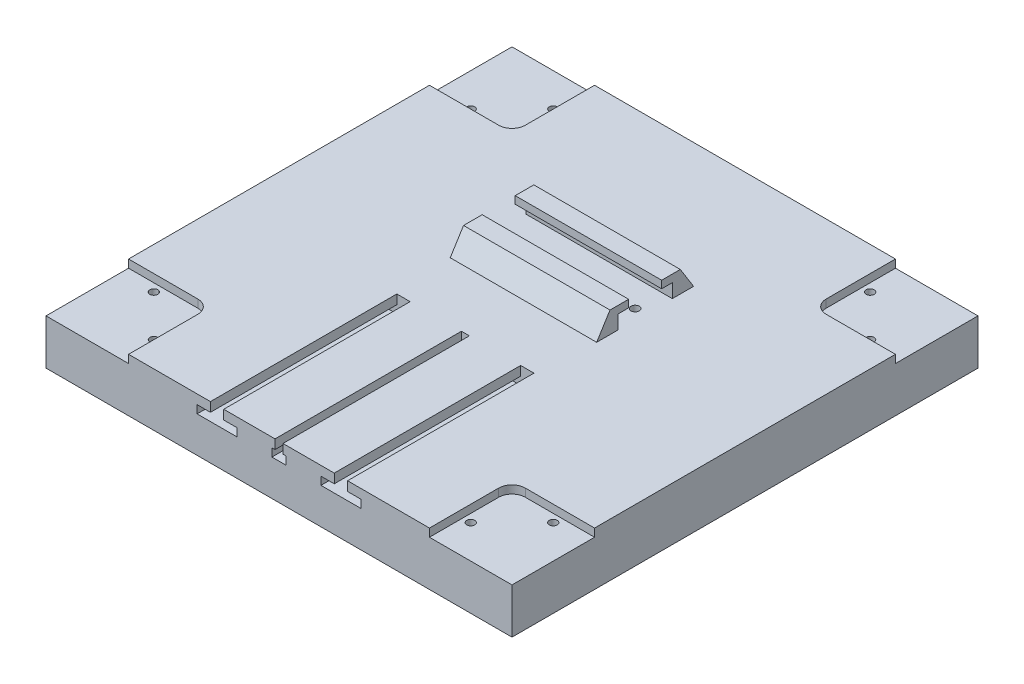
SolidWorks part; units mm, degrees
ref_plane "Front Plane" through (0, 0, 0) normal (0, 0, 1) x (1, 0, 0)
ref_plane "Top Plane" through (0, 0, 0) normal (0, 1, 0) x (1, 0, 0)
ref_plane "Right Plane" through (0, 0, 0) normal (1, 0, 0) x (0, 0, -1)
sketch "Sketch1" plane through (0, 0, 0) normal (0, 1, 0) x (1, 0, 0)
  line L0 (0, 87.5) -> (0, -87.5) construction
  line L1 (-87.5, 87.5) -> (87.5, 87.5)
  line L2 (-87.5, 87.5) -> (-87.5, -87.5)
  line L3 (-87.5, -87.5) -> (87.5, -87.5)
  line L4 (87.5, 87.5) -> (87.5, -87.5)
  line L5 (-87.5, 87.5) -> (87.5, -87.5) construction
  line L6 (-87.5, -87.5) -> (87.5, 87.5) construction
  line L15 (-87.5, 0) -> (87.5, 0) construction
  point P0 (0, 0)
  dimension "D1" = 175
  dimension "D2" = 175
extrude "Boss-Extrude2" add sketch "Sketch1" along normal blind 20
sketch "Sketch7" plane through (0, 20, 0) normal (0, 1, 0) x (1, 0, 0)
  line L0 (0, 87.5) -> (0, -87.5) construction
  line L1 (-87.5, 87.5) -> (-56.5, 87.5)
  line L2 (-87.5, 87.5) -> (-87.5, 56.5)
  line L3 (-87.5, 56.5) -> (-61.5, 56.5)
  line L4 (-56.5, 87.5) -> (-56.5, 61.5)
  line L5 (87.5, 87.5) -> (-87.5, 87.5) construction
  line L6 (-87.5, -87.5) -> (87.5, -87.5) construction
  line L7 (-87.5, 0) -> (87.5, 0) construction
  line L8 (-87.5, 87.5) -> (-87.5, -87.5) construction
  line L9 (87.5, -87.5) -> (87.5, 87.5) construction
  line L10 (87.5, 56.5) -> (61.5, 56.5)
  line L11 (56.5, 87.5) -> (56.5, 61.5)
  line L12 (87.5, 87.5) -> (56.5, 87.5)
  line L13 (87.5, 87.5) -> (87.5, 56.5)
  line L14 (87.5, -87.5) -> (87.5, -56.5)
  line L15 (87.5, -87.5) -> (56.5, -87.5)
  line L16 (56.5, -87.5) -> (56.5, -61.5)
  line L17 (87.5, -56.5) -> (61.5, -56.5)
  line L18 (-56.5, -87.5) -> (-56.5, -61.5)
  line L19 (-87.5, -56.5) -> (-61.5, -56.5)
  line L20 (-87.5, -87.5) -> (-87.5, -56.5)
  line L21 (-87.5, -87.5) -> (-56.5, -87.5)
  arc A0 (-61.5, 56.5) -> (-56.5, 61.5) centre (-61.5, 61.5) ccw
  arc A1 (61.5, 56.5) -> (56.5, 61.5) centre (61.5, 61.5) cw
  arc A2 (61.5, -56.5) -> (56.5, -61.5) centre (61.5, -61.5) ccw
  arc A3 (-61.5, -56.5) -> (-56.5, -61.5) centre (-61.5, -61.5) cw
  point P7 (-56.5, 56.5)
  point P38 (-56.5, -56.5)
  dimension "D3" = 5
  dimension "D1" = 31
  dimension "D2" = 31
extrude "Cut-Extrude6" cut sketch "Sketch7" against normal blind 3
sketch "Sketch8" plane through (0, 17, 0) normal (0, 1, 0) x (1, 0, 0)
  line L0 (-75, -62.5) -> (-75, -56.5) construction
  line L5 (-61.5, -56.5) -> (-87.5, -56.5) construction
  line L6 (-62.5, -75) -> (-56.5, -75) construction
  line L7 (-56.5, -87.5) -> (-56.5, -61.5) construction
  line L8 (-87.5, -87.5) -> (-56.5, -87.5) construction
  line L9 (-87.5, -56.5) -> (-87.5, -87.5) construction
  line L10 (0, 87.5) -> (0, -87.5) construction
  line L11 (56.5, 87.5) -> (-56.5, 87.5) construction
  line L12 (-56.5, -87.5) -> (56.5, -87.5) construction
  line L13 (62.5, -75) -> (56.5, -75) construction
  line L14 (75, -62.5) -> (75, -56.5) construction
  line L15 (-87.5, 0) -> (87.5, 0) construction
  line L16 (-87.5, 56.5) -> (-87.5, -56.5) construction
  line L17 (87.5, -56.5) -> (87.5, 56.5) construction
  circle A0 centre (-75, -59.5) radius 1.5
  circle A1 centre (-59.5, -75) radius 1.5
  circle A2 centre (59.5, -75) radius 1.5
  circle A3 centre (75, -59.5) radius 1.5
  circle A4 centre (59.5, 75) radius 1.5
  circle A5 centre (75, 59.5) radius 1.5
  circle A6 centre (-59.5, 75) radius 1.5
  circle A7 centre (-75, 59.5) radius 1.5
  dimension "D3" = 3
  dimension "D4" = 3
  dimension "D1" = 28
  dimension "D2" = 28
  dimension "D5" = 12.5
  dimension "D6" = 12.5
extrude "Cut-Extrude7" cut sketch "Sketch8" against normal up to next
sketch "Sketch9" plane through (0, 0, 87.5) normal (0, 0, 1) x (1, 0, 0)
  line L0 (0, 20) -> (0, 0) construction
  line L1 (-56.5, 20) -> (56.5, 20) construction
  line L2 (0, 10) -> (-46.5, 10) construction
  line L3 (-46.5, 20) -> (46.5, 20)
  line L4 (-46.5, 20) -> (-46.5, 0)
  line L5 (-46.5, 0) -> (46.5, 0)
  line L6 (46.5, 20) -> (46.5, 0)
  line L7 (-46.5, 20) -> (46.5, 0) construction
  line L8 (-46.5, 0) -> (46.5, 20) construction
  line L9 (-46.5, 10) -> (0, 10) construction
  line L10 (-20.75, 16.5) -> (-15.75, 16.5)
  line L11 (-23.25, 10) -> (-23.25, 20) construction
  line L12 (-30.75, 16.5) -> (-25.75, 16.5)
  line L13 (-30.75, 16.5) -> (-30.75, 13.5)
  line L14 (-30.75, 13.5) -> (-15.75, 13.5)
  line L15 (-15.75, 16.5) -> (-15.75, 13.5)
  line L16 (-30.75, 16.5) -> (-15.75, 13.5) construction
  line L17 (-30.75, 13.5) -> (-15.75, 16.5) construction
  line L18 (-25.75, 20) -> (-20.75, 20)
  line L19 (-25.75, 20) -> (-25.75, 16.5)
  line L21 (-20.75, 20) -> (-20.75, 16.5)
  line L22 (-25.75, 20) -> (-20.75, 16.5) construction
  line L23 (-25.75, 16.5) -> (-20.75, 20) construction
  line L24 (25.75, 16.5) -> (20.75, 20) construction
  line L25 (25.75, 20) -> (20.75, 16.5) construction
  line L26 (30.75, 13.5) -> (15.75, 16.5) construction
  line L27 (30.75, 16.5) -> (15.75, 13.5) construction
  line L28 (20.75, 20) -> (20.75, 16.5)
  line L29 (25.75, 20) -> (25.75, 16.5)
  line L30 (25.75, 20) -> (20.75, 20)
  line L31 (15.75, 16.5) -> (15.75, 13.5)
  line L32 (30.75, 13.5) -> (15.75, 13.5)
  line L33 (30.75, 16.5) -> (30.75, 13.5)
  line L34 (30.75, 16.5) -> (25.75, 16.5)
  line L35 (20.75, 16.5) -> (15.75, 16.5)
  line L36 (-15.75, 15) -> (15.75, 15) construction
  line L37 (1.5, 16.5) -> (2.65, 16.5)
  line L38 (-2.65, 16.5) -> (-1.5, 16.5)
  line L39 (-2.65, 16.5) -> (-2.65, 13.5)
  line L40 (-2.65, 13.5) -> (2.65, 13.5)
  line L41 (2.65, 16.5) -> (2.65, 13.5)
  line L42 (-2.65, 16.5) -> (2.65, 13.5) construction
  line L43 (-2.65, 13.5) -> (2.65, 16.5) construction
  line L44 (-1.5, 20) -> (1.5, 20)
  line L45 (-1.5, 20) -> (-1.5, 16.5)
  line L47 (1.5, 20) -> (1.5, 16.5)
  line L48 (-1.5, 20) -> (1.5, 16.5) construction
  line L49 (-1.5, 16.5) -> (1.5, 20) construction
  point P5 (0, 10)
  point P13 (-23.25, 15)
  point P19 (-23.25, 18.25)
  point P32 (23.25, 18.25)
  point P33 (23.25, 15)
  point P36 (0, 15)
  point P41 (0, 18.25)
  dimension "D1" = 93
  dimension "D2" = 20
  dimension "D3" = 3
  dimension "D4" = 15
  dimension "D5" = 3.5
  dimension "D6" = 5
  dimension "D7" = 5.3
  dimension "D8" = 3
  dimension "D9" = 3.5
  dimension "D10" = 3
  dimension "D11" = 46.5
extrude "Cut-Extrude8" cut sketch "Sketch9" against normal blind 70 contours L21 L3 L19 L12 L13 L14 L15 L10 | L28 L35 L31 L32 L33 L34 L29 L3 | L38 L45 L44 L47 L37 L41 L40 L39 region at (-23.25, 15.91, 87.5) region at (23.25, 15.91, 87.5)
sketch "Sketch10" plane through (0, 20, 0) normal (0, 1, 0) x (1, 0, 0)
  line L0 (56.5, 87.5) -> (-56.5, 87.5) construction
  line L1 (-23.75, 22.5) -> (23.75, 22.5) construction
  line L3 (87.5, -56.5) -> (87.5, 56.5) construction
  circle A0 centre (-23.75, 22.5) radius 1.55
  circle A1 centre (23.75, 22.5) radius 1.55
  point P2 (0, 87.5)
  point P3 (0, 22.5)
  point P7 (0, 32.5)
  dimension "D1" = 3.1
  dimension "D2" = 3.1
  dimension "D3" = 47.5
  dimension "D4" = 55
  dimension "D5" = 87.5
extrude "Cut-Extrude9" cut sketch "Sketch10" against normal up to next
sketch "Sketch11" plane through (0, 20, 0) normal (0, 1, 0) x (1, 0, 0)
  line L0 (-23.75, 22.5) -> (23.75, 22.5) construction
  line L14 (-27.5, 35.7) -> (27.5, 35.7)
  line L15 (-27.5, 35.7) -> (-27.5, 9.3)
  line L20 (-27.5, 9.3) -> (27.5, 9.3)
  line L21 (27.5, 35.7) -> (27.5, 9.3)
  line L22 (-27.5, 35.7) -> (27.5, 9.3) construction
  line L23 (-27.5, 9.3) -> (27.5, 35.7) construction
  point P4 (0, 22.5)
  point P5 (0, 22.5)
  point P6 (0, 22.5)
  point P10 (0, 22.5)
  point P21 (0, 22.5)
  dimension "D1" = 26.4
  dimension "D2" = 55
extrude "Boss-Extrude4" add sketch "Sketch11" along normal blind 8
sketch "Sketch14" plane through (27.5, 0, 0) normal (1, 0, 0) x (0, 0, -1)
  line L0 (9.3, 24) -> (35.7, 24) construction
  line L4 (12.3, 28) -> (32.7, 28)
  line L5 (12.3, 28) -> (12.3, 20)
  line L6 (12.3, 20) -> (32.7, 20)
  line L7 (32.7, 28) -> (32.7, 20)
  line L8 (12.3, 28) -> (32.7, 20) construction
  line L9 (12.3, 20) -> (32.7, 28) construction
  line L10 (12.3, 20) -> (32.7, 20)
  line L11 (12.3, 20) -> (12.3, 25.2)
  line L12 (12.3, 25.2) -> (32.7, 25.2)
  line L13 (32.7, 20) -> (32.7, 25.2)
  line L15 (9.3, 28) -> (9.3, 20) construction
  line L16 (35.7, 28) -> (35.7, 20) construction
  point P6 (22.5, 24)
  line M10 (9.3, 20) -> (35.7, 20)
  dimension "D1" = 20.4
  dimension "D2" = 8
  dimension "D3" = 20.4
  dimension "D4" = 5.2
extrude "Cut-Extrude10" cut sketch "Sketch14" against normal up to next contours L12 L5 L7 M10 region at (27.5, 22.6, -22.5)
sketch "Sketch15" plane through (27.5, 0, 0) normal (1, 0, 0) x (0, 0, -1)
  line L0 (22.5, 28) -> (22.5, 25.2) construction
  line L1 (35.7, 28) -> (9.3, 28) construction
  line L2 (12.3, 25.2) -> (32.7, 25.2) construction
  line L4 (16.3, 28) -> (28.7, 28)
  line L5 (16.3, 28) -> (16.3, 25.2)
  line L6 (16.3, 25.2) -> (28.7, 25.2)
  line L7 (28.7, 28) -> (28.7, 25.2)
  line L8 (16.3, 28) -> (28.7, 25.2) construction
  line L9 (16.3, 25.2) -> (28.7, 28) construction
  point P6 (22.5, 26.6)
  dimension "D1" = 2.8
  dimension "D2" = 12.4
extrude "Cut-Extrude11" cut sketch "Sketch15" against normal up to next
sketch "Sketch17" plane through (27.5, 0, 0) normal (1, 0, 0) x (0, 0, -1)
  line L0 (4.3, 20) -> (9.3, 28)
  line L1 (9.3, 28) -> (4.3, 28)
  line L2 (9.3, 28) -> (9.3, 20)
  line L3 (9.3, 20) -> (4.3, 20)
  line L4 (4.3, 28) -> (4.3, 20)
  line M5 (9.3, 28) -> (9.3, 20)
  dimension "D1" = 5
  dimension "D2" = 8
extrude "Boss-Extrude7" add sketch "Sketch17" against normal blind 55 contours L3 L0 M5 region at (27.5, 22.6667, -7.6333)
sketch "Sketch18" plane through (27.5, 0, 0) normal (1, 0, 0) x (0, 0, -1)
  line L0 (35.7, 28) -> (40.7, 20)
  line L1 (35.7, 28) -> (40.7, 28)
  line L2 (35.7, 28) -> (35.7, 20)
  line L3 (35.7, 20) -> (40.7, 20)
  line L4 (40.7, 28) -> (40.7, 20)
  line M7 (35.7, 20) -> (35.7, 28)
  dimension "D1" = 5
  dimension "D2" = 8
extrude "Boss-Extrude8" add sketch "Sketch18" against normal blind 55 contours L3 L0 M7 region at (27.5, 22.6667, -37.3667)
